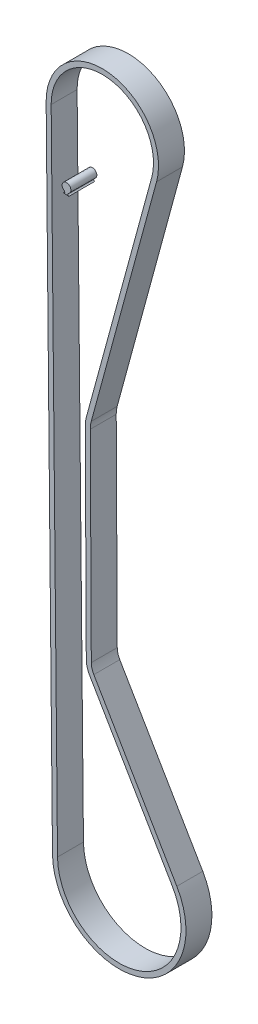
SolidWorks part; units mm, degrees
ref_plane "Front Plane" through (0, 0, 0) normal (0, 0, 1) x (1, 0, 0)
ref_plane "Top Plane" through (0, 0, 0) normal (0, 1, 0) x (1, 0, 0)
ref_plane "Right Plane" through (0, 0, 0) normal (1, 0, 0) x (0, 0, -1)
sketch "Sketch2" plane through (0, 0, 0) normal (0, 0, 1) x (1, 0, 0)
  line L0 (0, 0) -> (1, 0) construction
  line L1 (0, 0) -> (0, 1) construction
  line L13 (-8.892, -238.9097) -> (-11.0945, -13.9502)
  line L20 (3.8199, -178.246) -> (32.617, -227.4342)
  line L22 (25.4916, -18.6557) -> (2.8388, -101.9263)
  line L23 (2.4744, -104.7079) -> (2.8307, -174.635)
  arc A4 (32.617, -227.4342) -> (-8.892, -238.9097) centre (13.3884, -238.6915) cw
  arc A7 (-11.0945, -13.9502) -> (25.4916, -18.6557) centre (7.5246, -13.768) cw
  arc A8 (2.8307, -174.635) -> (3.8199, -178.246) centre (10.0507, -174.5982) ccw
  arc A11 (2.8388, -101.9263) -> (2.4744, -104.7079) centre (12.8693, -104.655) ccw
extrude "Extrude-Thin1" add sketch "Sketch2" along normal blind 9 thin thin type two direction wall 0.87 second wall 0.87
sketch "Sketch3" plane through (0, 0, 0) normal (0, 0, -1) x (-1, 0, 0)
  line L0 (5.9606, -38.344) -> (4.0787, -38.4465)
  line L1 (10.2246, -13.9417) -> (8.0221, -238.9012) construction
  line L3 (5.9606, -38.344) -> (-14.491, -39.4571) construction
  arc A0 (5.7098, -37.5497) -> (4.2418, -37.6296) centre (4.9032, -36.2555) ccw
  arc A1 (5.9606, -38.344) -> (5.7098, -37.5497) centre (5.9373, -37.9147) cw
  arc A2 (4.0787, -38.4465) -> (4.2418, -37.6296) centre (4.0553, -38.0171) ccw
  point P2 (6.4282, -36.2555)
  dimension "D1" = 3.05
  dimension "D3" = 0.43
  dimension "D2" = 2.06
extrude "Boss-Extrude1" add sketch "Sketch3" against normal up to surface (9 mm away) up to face at (7.9441, -133.0203, 9)
pattern_curve "CrvPattern1" rebuild error yes driven by "Sketch2" parameters "D1"=119, "D3"=5, "D2"=1, "D4"=50
